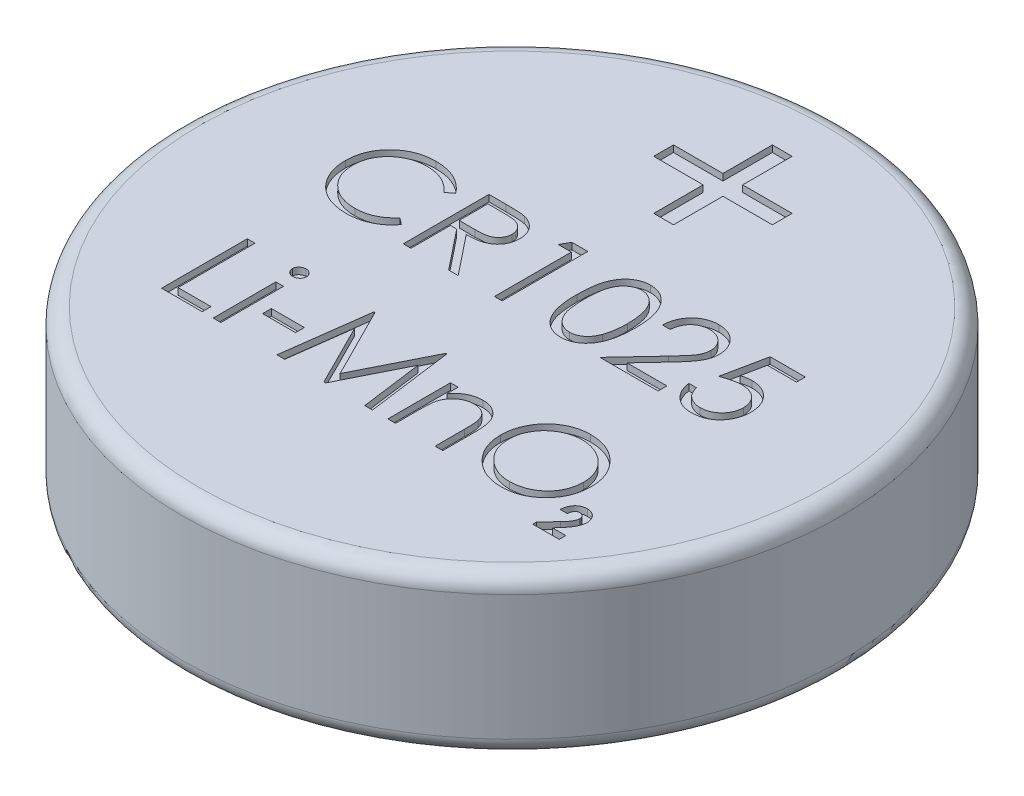
SolidWorks part; units mm, degrees
ref_plane "Front Plane" through (0, 0, 0) normal (0, 0, 1) x (1, 0, 0)
ref_plane "Top Plane" through (0, 0, 0) normal (0, 1, 0) x (1, 0, 0)
ref_plane "Right Plane" through (0, 0, 0) normal (1, 0, 0) x (0, 0, -1)
sketch "Sketch1" plane through (0, 0, 0) normal (0, 1, 0) x (1, 0, 0)
  circle A0 centre (0, 0) radius 5
  dimension "D1" = 10
extrude "Boss-Extrude1" add sketch "Sketch1" along normal blind 2.4 from offset 0.1
sketch "Sketch2" plane through (0, 0, 0) normal (0, -1, 0) x (1, 0, 0)
  circle A0 centre (0, 0) radius 4
  dimension "D1" = 8
extrude "Boss-Extrude2" add sketch "Sketch2" against normal up to next
fillet "Fillet1" radius 0.25 2 edges at (0, 0.1, 5) (0, 2.5, 5)
fillet "Fillet2" radius 0.1 1 edges at (0, 0, -4)
sketch "Sketch3" plane through (0, 2.5, 0) normal (0, 1, 0) x (1, 0, 0)
  line L0 (-7.1858, 0) -> (7.1858, 0) construction
  line L1 (3, -2.7) -> (5.278, -2.7) construction
  line L2 (0.15, 4.1) -> (-0.15, 4.1) construction
  line L3 (0.15, 4.1) -> (0.15, 2.3) construction
  line L4 (0.15, 2.3) -> (-0.15, 2.3) construction
  line L5 (-0.15, 4.1) -> (-0.15, 2.3) construction
  line L6 (0.15, 4.1) -> (-0.15, 2.3) construction
  line L7 (0.15, 2.3) -> (-0.15, 4.1) construction
  line L8 (-0.9, 3.35) -> (0.9, 3.35) construction
  line L9 (-0.9, 3.35) -> (-0.9, 3.05) construction
  line L10 (-0.9, 3.05) -> (0.9, 3.05) construction
  line L11 (0.9, 3.35) -> (0.9, 3.05) construction
  line L12 (-0.9, 3.35) -> (0.9, 3.05) construction
  line L13 (-0.9, 3.05) -> (0.9, 3.35) construction
  text T0 "CR1025\r\nLi-MnO" font "Century Gothic" height 1.3
  text T1 "<b>2</b>" font "Century Gothic" height 0.6
  point P4 (0, 0)
  point P5 (0, 3.2)
  point P10 (0, 3.2)
  dimension "D1" = 0.3
  dimension "D2" = 1.8
  dimension "D3" = 3.2
  dimension "D4" = 2.7
  dimension "D5" = 3
extrude "Cut-Extrude1" cut sketch "Sketch3" against normal blind 0.1
sketch "Sketch4" plane through (0, 2.5, 0) normal (0, 1, 0) x (1, 0, 0)
  line L0 (-0.9, 3.35) -> (-0.9, 3.05) construction
  line L1 (-0.9, 3.35) -> (0.9, 3.35) construction
  line L2 (-0.15, 4.1) -> (-0.15, 2.3) construction
  line L3 (0.15, 4.1) -> (-0.15, 4.1) construction
  line L4 (0.15, 4.1) -> (0.15, 2.3) construction
  line L5 (0.9, 3.35) -> (0.9, 3.05) construction
  line L6 (-0.9, 3.05) -> (0.9, 3.05) construction
  line L7 (0.15, 2.3) -> (-0.15, 2.3) construction
  line L8 (-0.9, 3.35) -> (-0.9, 3.05)
  line L9 (-0.9, 3.35) -> (-0.15, 3.35)
  line L10 (-0.15, 4.1) -> (-0.15, 3.35)
  line L11 (0.15, 4.1) -> (-0.15, 4.1)
  line L12 (0.15, 4.1) -> (0.15, 3.35)
  line L13 (0.9, 3.35) -> (0.9, 3.05)
  line L14 (-0.9, 3.05) -> (-0.15, 3.05)
  line L15 (0.15, 2.3) -> (-0.15, 2.3)
  line L16 (0.15, 3.35) -> (0.9, 3.35)
  line L17 (0.15, 3.05) -> (0.9, 3.05)
  line L18 (-0.15, 3.05) -> (-0.15, 2.3)
  line L19 (0.15, 3.05) -> (0.15, 2.3)
extrude "Cut-Extrude2" cut sketch "Sketch4" against normal blind 0.1
